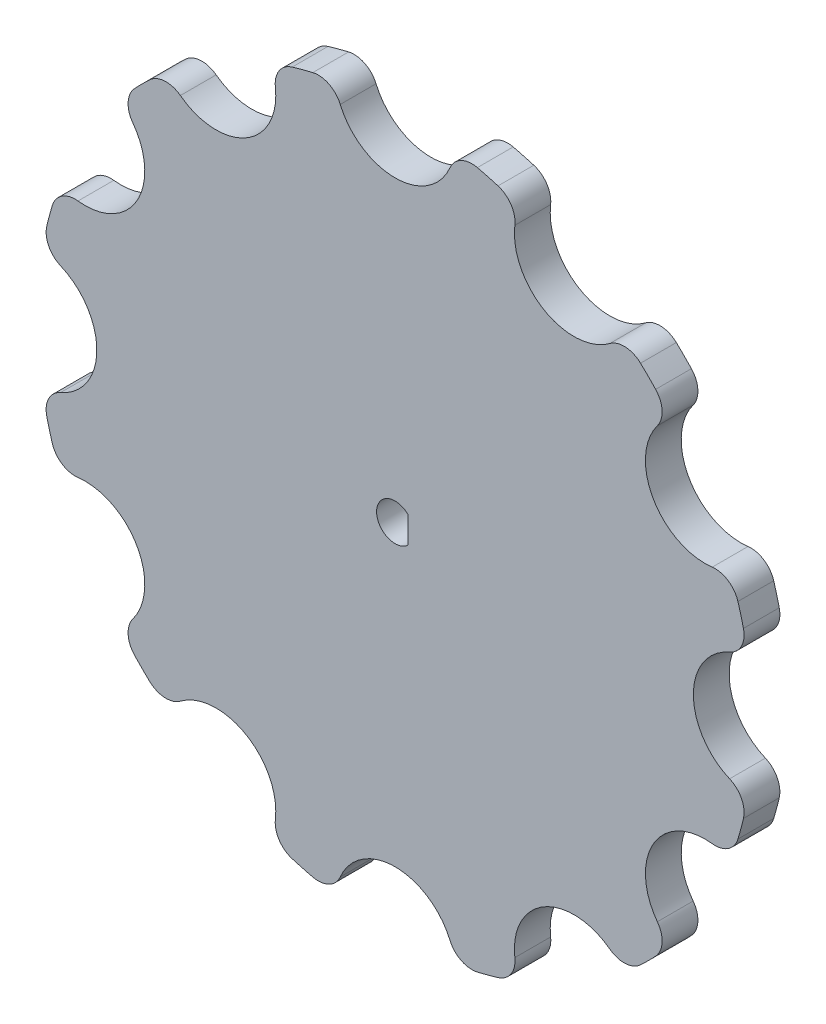
SolidWorks part; units mm, degrees
ref_plane "Front Plane" through (0, 0, 0) normal (0, 0, 1) x (1, 0, 0)
ref_plane "Top Plane" through (0, 0, 0) normal (0, 1, 0) x (1, 0, 0)
ref_plane "Right Plane" through (0, 0, 0) normal (1, 0, 0) x (0, 0, -1)
sketch "Sketch1" plane through (0, 0, 0) normal (0, 0, 1) x (1, 0, 0)
  line L0 (0, 25) -> (0, 30) construction
  circle A0 centre (0, 0) radius 30
  circle A1 centre (0, 0) radius 25 construction
  circle A2 centre (0, 30) radius 5
  circle A3 centre (15, 25.9808) radius 5
  circle A4 centre (25.9808, 15) radius 5
  circle A5 centre (30, 0) radius 5
  circle A6 centre (25.9808, -15) radius 5
  circle A7 centre (15, -25.9808) radius 5
  circle A8 centre (0, -30) radius 5
  circle A9 centre (-15, -25.9808) radius 5
  circle A10 centre (-25.9808, -15) radius 5
  circle A11 centre (-30, 0) radius 5
  circle A12 centre (-25.9808, 15) radius 5
  circle A13 centre (-15, 25.9808) radius 5
  point P31 (0, 0)
  dimension "D1" = 60
  dimension "D2" = 50
  dimension "D3" = 12
extrude "Boss-Extrude1" add sketch "Sketch1" along normal blind 3 contours A13 A0 A12 A11 A10 A9 A8 A7 A6 A5 A4 A3 A2 region at (0, 0, 0)
fillet "Fillet1" radius 2 4 edges at (-23.1286, 19.1067, 1.5) (-19.1067, 23.1286, 1.5) (-4.9826, 29.5833, 1.5) (-10.4766, 28.1112, 1.5)
fillet "Fillet2" radius 2 20 edges at (-28.1112, 10.4766, 1.5) (-29.5833, 4.9826, 1.5) (-29.5833, -4.9826, 1.5) (-28.1112, -10.4766, 1.5) (-23.1286, -19.1067, 1.5) (-19.1067, -23.1286, 1.5) (-10.4766, -28.1112, 1.5) (-4.9826, -29.5833, 1.5) (4.9826, -29.5833, 1.5) (10.4766, -28.1112, 1.5) (19.1067, -23.1286, 1.5) (23.1286, -19.1067, 1.5) (28.1112, -10.4766, 1.5) (29.5833, -4.9826, 1.5) (29.5833, 4.9826, 1.5) (28.1112, 10.4766, 1.5) (23.1286, 19.1067, 1.5) (19.1067, 23.1286, 1.5) (4.9826, 29.5833, 1.5) (10.4766, 28.1112, 1.5)
sketch "Sketch4" plane through (0, 0, 0) normal (0, 0, 1) x (1, 0, 0)
  circle A2 centre (0, 0) radius 3.05
extrude "Boss-Extrude3" add sketch "Sketch4" against normal blind 2
sketch "Sketch2" plane through (0, 0, 0) normal (0, 0, -1) x (-1, 0, 0)
  line L0 (-1.55, 0) -> (-1.1, 0)
  line L1 (-1.1, 0) -> (-1.1, 1.092)
  line L2 (-1.1, 1.092) -> (-1.1, -1.092)
  circle A0 centre (0, 0) radius 1.55
  dimension "D1" = 3.1
  dimension "D2" = 0.45
extrude "Cut-Extrude1" cut sketch "Sketch2" along normal blind 17 from surface contours L2 A0 L1 region at (-0.1264, 0, 0) starting at face at (0, 0, 3)
